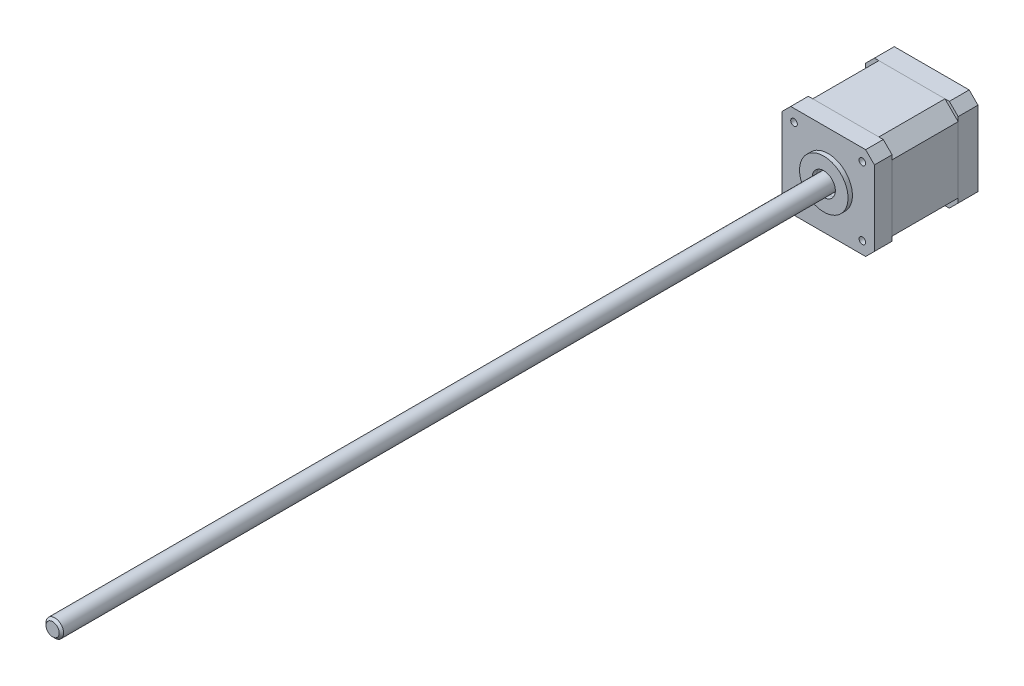
SolidWorks part; units mm, degrees
material "AISI 304"
ref_plane "前基準面" through (0, 0, 0) normal (0, 0, 1) x (1, 0, 0)
ref_plane "上基準面" through (0, 0, 0) normal (0, 1, 0) x (1, 0, 0)
ref_plane "右基準面" through (0, 0, 0) normal (1, 0, 0) x (0, 0, -1)
sketch "草圖1" plane through (0, 0, 0) normal (0, 0, 1) x (1, 0, 0)
  line L1 (-21, -21) -> (21, -21)
  line L2 (-21, -21) -> (-21, 21)
  line L3 (-21, 21) -> (21, 21)
  line L4 (21, -21) -> (21, 21)
  line L5 (-21, -21) -> (21, 21) construction
  line L6 (-21, 21) -> (21, -21) construction
  point P0 (0, 0)
  dimension "D1" = 42
  dimension "D2" = 42
extrude "填料-伸長1" add sketch "草圖1" along normal mid plane 30
chamfer "導角1" distance 6 angle 45 4 edges at (21, -21, 0) (-21, -21, 0) (-21, 21, 0) (21, 21, 0)
sketch "草圖15" plane through (0, 0, 15) normal (0, 0, 1) x (1, 0, 0)
  line L0 (15, 21) -> (-15, 21) construction
  line L1 (-21, -21) -> (21, -21)
  line L2 (-21, -21) -> (-21, 21)
  line L3 (-21, 21) -> (21, 21)
  line L4 (21, -21) -> (21, 21)
  line L5 (-21, -21) -> (21, 21) construction
  line L6 (-21, 21) -> (21, -21) construction
  line L7 (21, -15) -> (21, 15) construction
  point P0 (0, 0)
extrude "填料-伸長11" add sketch "草圖15" along normal blind 8 separate body
sketch "草圖16" plane through (0, 0, -15) normal (0, 0, -1) x (-1, 0, 0)
  line L1 (-21, -21) -> (21, -21)
  line L2 (-21, -21) -> (-21, 21)
  line L3 (-21, 21) -> (21, 21)
  line L4 (21, -21) -> (21, 21)
  line L5 (-21, -21) -> (21, 21) construction
  line L6 (-21, 21) -> (21, -21) construction
  line L8 (-15, 21) -> (15, 21) construction
  line L9 (21, 15) -> (21, -15) construction
  point P0 (0, 0)
extrude "填料-伸長12" add sketch "草圖16" along normal blind 9 separate body
chamfer "導角2" distance 4 angle 45 4 edges at (-21, -21, 19) (21, -21, 19) (21, 21, 19) (-21, 21, 19)
chamfer "導角3" distance 4 angle 45 4 edges at (-21, -21, -19.5) (21, -21, -19.5) (-21, 21, -19.5) (21, 21, -19.5)
sketch "草圖2" plane through (0, 0, 23) normal (0, 0, 1) x (1, 0, 0)
  circle A0 centre (0, 0) radius 11
  dimension "D1" = 22
extrude "填料-伸長2" add sketch "草圖2" along normal blind 2
sketch "草圖3" plane through (0, 0, 25) normal (0, 0, 1) x (1, 0, 0)
  circle A0 centre (0, 0) radius 5.25
  dimension "D1" = 10.5
extrude "除料-伸長1" cut sketch "草圖3" along direction (0, 0, -1) on the side against the normal blind 5
sketch "草圖6" plane through (0, 0, 23) normal (0, 0, 1) x (1, 0, 0)
  circle A0 centre (0, 0) radius 4
  dimension "D1" = 8
extrude "填料-伸長9" add sketch "草圖6" along direction (0, 0, 1) on the side of the normal offset from surface (352 mm away) 350 separate body up to face at (5.25, 0, 25) offset beyond the face yes
sketch "草圖8" plane through (0, 0, 23) normal (0, 0, 1) x (1, 0, 0)
  line L0 (0, 0) -> (0, 15.5) construction
  line L1 (0, 15.5) -> (-15.5, 15.5) construction
  circle A0 centre (-15.5, 15.5) radius 1.5
  dimension "D3" = 3
  dimension "D1" = 15.5
  dimension "D2" = 15.5
extrude "除料-伸長3" cut sketch "草圖8" against normal blind 4.5
pattern_circular "環狀複製排列1" count 4 over 360 about axis through (0, 0, 23) along (0, 0, 1) of "除料-伸長3"
sketch "草圖21" plane through (0, 0, 375) normal (0, 0, 1) x (1, 0, 0)
  circle A0 centre (0, 0) radius 4
  circle A1 centre (0, 0) radius 4 construction
curve "螺旋曲線/渦捲線1" pitch 8 height 350 turns 43.75
sketch "草圖17" plane through (0, 0, 0) normal (1, 0, 0) x (0, 0, -1)
  line L5 (-375, 3.2536) -> (-375, 4) construction
  line L6 (-375, 4) -> (-375, -4) construction
  line L9 (-374.8, 3.2536) -> (-374.6, 4)
  line L10 (-375.4, 4) -> (-374.6, 4)
  line L11 (-375.2, 3.2536) -> (-374.8, 3.2536)
  line L12 (-23, 4) -> (-375, 4) construction
  line L13 (-375.2, 3.2536) -> (-375.4, 4)
  point P3 (-375, 3.2536)
  dimension "D1" = 0.2
  dimension "D2" = 0.4
  dimension "D3" = 15
sweep "除料-掃出4" [suppressed] cut profiles "草圖17" path "螺旋曲線/渦捲線1"
pattern_circular "環狀複製排列2" [suppressed] count 4 over 360 of bodies 117
chamfer "導角4" distance 1 angle 45 1 edges at (4, 0, 375)
